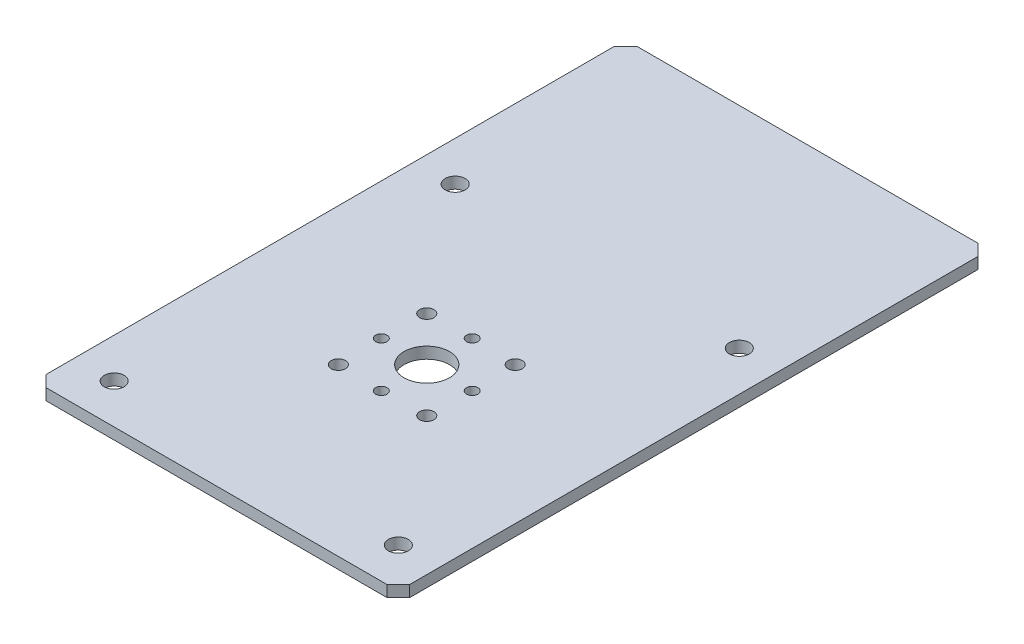
SolidWorks part; units mm, degrees
material "1060 Alloy"
ref_plane "Front Plane" through (0, 0, 0) normal (0, 0, 1) x (1, 0, 0)
ref_plane "Top Plane" through (0, 0, 0) normal (0, 1, 0) x (1, 0, 0)
ref_plane "Right Plane" through (0, 0, 0) normal (1, 0, 0) x (0, 0, -1)
sketch "Sketch1" plane through (0, 0, 0) normal (0, 0, 1) x (1, 0, 0)
  line L0 (-32, 0) -> (32, 0)
  line L1 (0, 0) -> (0, 13.1388) construction
  dimension "D1" = 64
sheet metal parameters "Sheet-Metal1" thickness 2 parameters "D1"=2
base flange "Base-Flange1" sketch "Sketch1" end condition blind depth 74 reverse direction no thickness 2 reverse thickness direction no bend radius 2
sketch "Sketch2" plane through (0, 0, 0) normal (0, 1, 0) x (1, 0, 0)
  line L0 (0, -7) -> (0, 0) construction
  line L1 (-25, -7) -> (25, -7) construction
  line L2 (-25, -7) -> (-25, -67) construction
  line L3 (-25, -67) -> (25, -67) construction
  line L4 (25, -7) -> (25, -67) construction
  line L5 (-25, -37) -> (-32, -37) construction
  line L6 (-32, -74) -> (32, -74) construction
  line L7 (-32, -74) -> (-32, 0) construction
  line L8 (32, -74) -> (32, 0) construction
  circle A0 centre (-25, -7) radius 1.75
  circle A1 centre (-25, -67) radius 1.75
  circle A2 centre (25, -67) radius 1.75
  circle A3 centre (25, -7) radius 1.75
  dimension "D1" = 3.5
  dimension "D3" = 7
  dimension "D2" = 7
extrude "Cut-Extrude1" cut sketch "Sketch2" against normal blind 10 normal cut yes
sketch "Sketch4" plane through (0, 0, 0) normal (0, 1, 0) x (1, 0, 0)
  line L0 (0, -37) -> (0, -74) construction
  line L1 (-32, -37) -> (0, -37) construction
  line L2 (-32, -74) -> (32, -74) construction
  line L3 (-32, -74) -> (-32, 0) construction
  circle A0 centre (0, -37) radius 4
  dimension "D1" = 8
extrude "Cut-Extrude2" cut sketch "Sketch4" against normal up to next normal cut yes
chamfer "Chamfer1" distance 2 angle 45 2 edges at (32, -1, 74) (-32, -1, 74)
sketch "Sketch7" plane through (0, 0, 0) normal (0, 1, 0) x (1, 0, 0)
  circle A0 centre (-8, -37) radius 1
  circle A1 centre (8, -37) radius 1
  circle A2 centre (0, -45) radius 1
  circle A3 centre (0, -29) radius 1
  circle A4 centre (-7.7782, -44.7782) radius 1.25
  circle A5 centre (-7.7782, -29.2218) radius 1.25
  circle A6 centre (7.7782, -29.2218) radius 1.25
  circle A7 centre (7.7782, -44.7782) radius 1.25
  dimension "D1" = 2.5
  dimension "D2" = 2
extrude "Cut-Extrude5" cut sketch "Sketch7" against normal up to next normal cut yes
sketch "Sketch8" plane through (0, 0, 0) normal (0, 1, 0) x (1, 0, 0)
  line L1 (-32, 0) -> (32, 0)
  line L2 (-32, 0) -> (-32, 30)
  line L3 (-32, 30) -> (32, 30)
  line L4 (32, 0) -> (32, 30)
  dimension "D1" = 30
base flange "Tab1" sketch "Sketch8" thickness 2 reverse thickness direction no parameters "D1"=2
chamfer "Chamfer2" distance 2 angle 45 2 edges at (32, -1, -30) (-32, -1, -30)
flat pattern "Flat-Pattern1" [suppressed]
sketch "Bend-Lines1" plane through (0, 0, 0) normal (0, 1, 0) x (-1, 0, 0)
